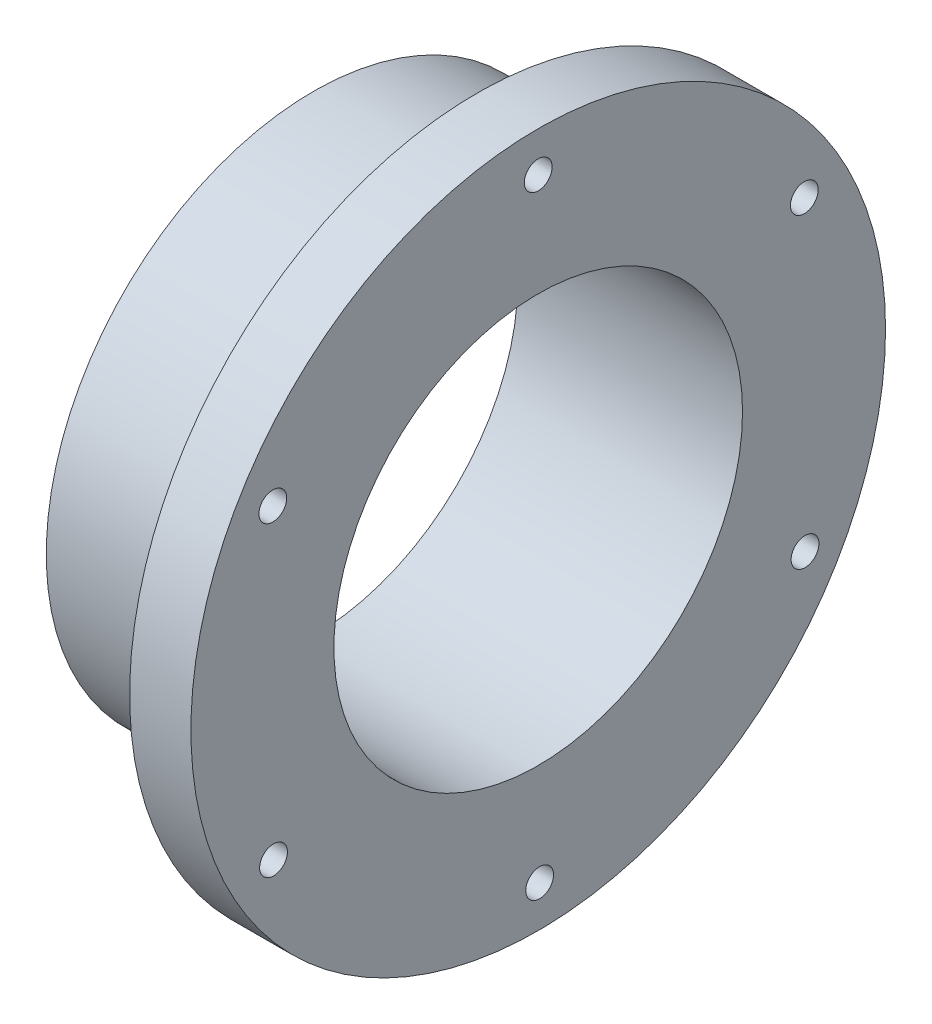
SolidWorks part; units mm, degrees
material "7075-O (SS)"
ref_plane "Front" through (0, 0, 0) normal (0, 0, 1) x (1, 0, 0)
ref_plane "Top" through (0, 0, 0) normal (0, 1, 0) x (1, 0, 0)
ref_plane "Right" through (0, 0, 0) normal (1, 0, 0) x (0, 0, -1)
sketch "Croquis1" plane through (0, 0, 0) normal (1, 0, 0) x (0, 0, -1)
  circle A0 centre (0, 0) radius 32.7
  circle A1 centre (0, 0) radius 25
  dimension "D1" = 65.4
  dimension "D2" = 50
extrude "Saliente-Extruir1" add sketch "Croquis1" along normal mid plane 5
sketch "Croquis2" plane through (0, 0, 0) normal (1, 0, 0) x (0, 0, -1)
  circle A2 centre (0, 0) radius 25
  circle A3 centre (0, 0) radius 32.7
  point P2 (9.0259, 8.2111)
  dimension "D1" = 50
  dimension "D2" = 65.4
extrude "Saliente-Extruir2" add sketch "Croquis2" along normal blind 25
sketch "Croquis5" plane through (25, 0, 0) normal (1, 0, 0) x (0, 0, -1)
  circle A0 centre (0, 0) radius 42.5
  circle A2 centre (0, 0) radius 32.7
  circle A3 centre (0, 0) radius 32.7 construction
  dimension "D1" = 85
extrude "Saliente-Extruir4" add sketch "Croquis5" against normal blind 7.5
hole_wizard "Taladro de margen para M31" positions "Croquis8" profile "Croquis9" hole size "M3" standard "Ansi Metric" end condition up to next
sketch "Croquis8" plane through (17.5, 0, 0) normal (-1, 0, 0) x (0, 0, 1)
  line L0 (0, -55) -> (0, 55) construction
  line L1 (0, 42.5) -> (0, 32.7) construction
  circle A0 centre (0, 0) radius 42.5 construction
  circle A1 centre (0, 0) radius 32.7 construction
  point P0 (0, 37.6)
  point P17 (0, 37.6)
  point P22 (32.476, 18.75)
  point P23 (32.3894, -18.8)
  point P24 (-0.1732, -37.5)
  point P25 (-32.6492, -18.65)
  point P26 (-32.5626, 18.9)
  dimension "D1" = 6
sketch "Croquis9" plane through (17.5, 37.6, 0) normal (0, 1, 0) x (0, 0, 1)
  line L0 (0, 0) -> (0, 7.5)
  line L1 (0, 7.5) -> (1.7, 7.5)
  line L2 (1.7, 7.5) -> (1.7, 0)
  line L5 (1.7, 0) -> (0, 0)
  line L11 (0, -6.35) -> (0, 107.95) construction
  dimension "Diámetro de taladro hasta el siguiente" = 3.4
  dimension "Profundidad de taladro hasta el siguiente" = 7.5
hole_wizard "Taladro de margen para M32" positions "Croquis10" profile "Croquis12" hole size "M3" standard "Ansi Metric"
sketch "Croquis10" plane through (-2.5, 0, 0) normal (-1, 0, 0) x (0, 0, 1)
  line L0 (0, -15.125) -> (0, 15.125) construction
  line L1 (15.125, 0) -> (-15.125, 0) construction
  point P0 (0, 28)
  point P11 (24.2487, 14)
  point P12 (24.2487, -14)
  point P13 (0, -28)
  point P15 (-24.2487, -14)
  point P16 (-24.2487, 14)
  point P17 (0, 28)
  point P18 (0, 0)
  dimension "D1" = 28
  dimension "D3" = 28
  dimension "D2" = 6
sketch "Croquis12" plane through (-2.5, 28, 0) normal (0, 1, 0) x (0, 0, 1)
  line L0 (0, 0) -> (0, 11.0215)
  line L1 (0, 11.0215) -> (1.7, 10)
  line L2 (1.7, 10) -> (1.7, 0)
  line L5 (1.7, 0) -> (0, 0)
  line L10 (0, 11.0215) -> (-1.7, 10) construction
  line L11 (0, -6.35) -> (0, 107.95) construction
  dimension "Diámetro de taladro" = 3.4
  dimension "Profundidad de taladro" = 10
  dimension "Ángulo de perforador" = 118
